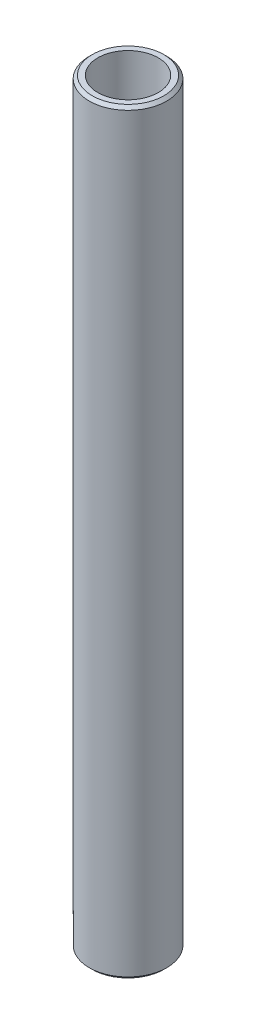
SolidWorks part; units mm, degrees
ref_plane "Front Plane" through (0, 0, 0) normal (0, 0, 1) x (1, 0, 0)
ref_plane "Top Plane" through (0, 0, 0) normal (0, 1, 0) x (1, 0, 0)
ref_plane "Right Plane" through (0, 0, 0) normal (1, 0, 0) x (0, 0, -1)
sketch "Sketch1" plane through (0, 0, 0) normal (0, 1, 0) x (1, 0, 0)
  circle A0 centre (0, 0) radius 17.5
  dimension "SHAFT_OD" = 35
extrude "Boss-Extrude1" add sketch "Sketch1" along normal blind 341.2431
sketch "Sketch2" plane through (0, 0, 0) normal (0, 1, 0) x (1, 0, 0)
  circle A0 centre (0, 0) radius 13.6205
  dimension "BORE_D" = 27.2411
extrude "Cut-Extrude1" cut sketch "Sketch2" along normal through all
chamfer "Chamfer1" distance 1.3658 angle 45 2 edges at (0, 341.2431, 17.5) (0, 0, 17.5)
